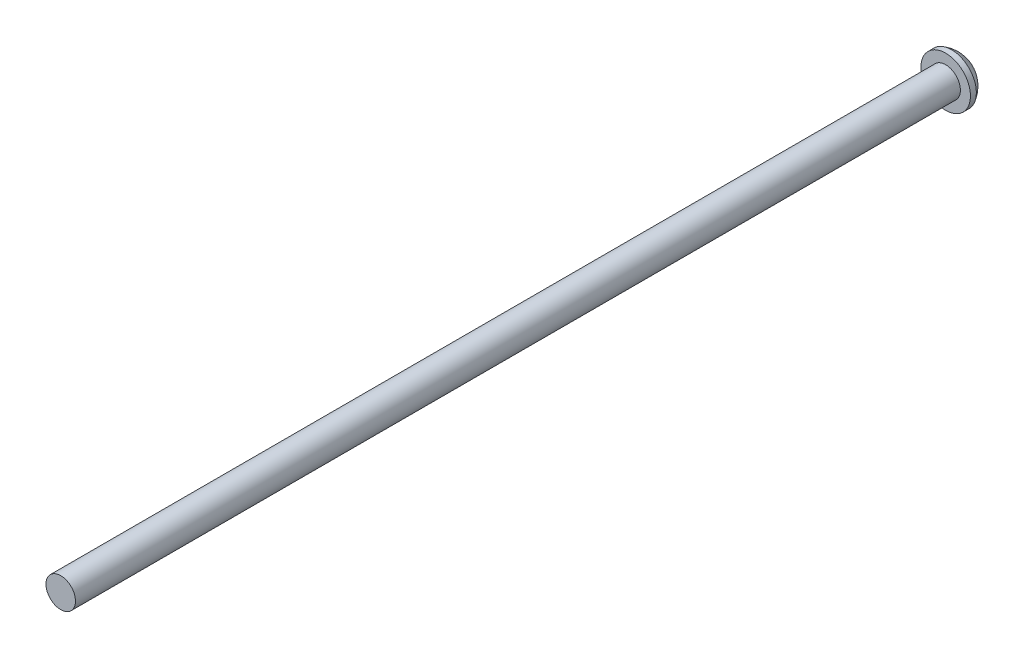
SolidWorks part; units mm, degrees
ref_plane "Front Plane" through (0, 0, 0) normal (0, 0, 1) x (1, 0, 0)
ref_plane "Top Plane" through (0, 0, 0) normal (0, 1, 0) x (1, 0, 0)
ref_plane "Right Plane" through (0, 0, 0) normal (1, 0, 0) x (0, 0, -1)
sketch "Sketch1" plane through (0, 0, 0) normal (0, 0, 1) x (1, 0, 0)
  circle A0 centre (0, 0) radius 0.5
  dimension "D1" = 1
extrude "Boss-Extrude1" add sketch "Sketch1" along normal blind 30
cosmetic thread "Cosmetic Thread1" parameters "D1"=5, "D2"=0.755
sketch "Sketch2" plane through (0, 0, 0) normal (0, 0, -1) x (-1, 0, 0)
  circle A0 centre (0, 0) radius 0.8408
extrude "Boss-Extrude2" add sketch "Sketch2" along normal blind 0.2
dome "Dome1" faces to dome 1 distance 0.5 reverse direction no elliptical dome no face at (-0.8408, 0, -0.2) parameters "D1"=0.5
scale "Scale1" scale about centroid uniform scaling yes scale factor 1.9329
scale "Scale2" scale about centroid uniform scaling yes scale factor 1.5
